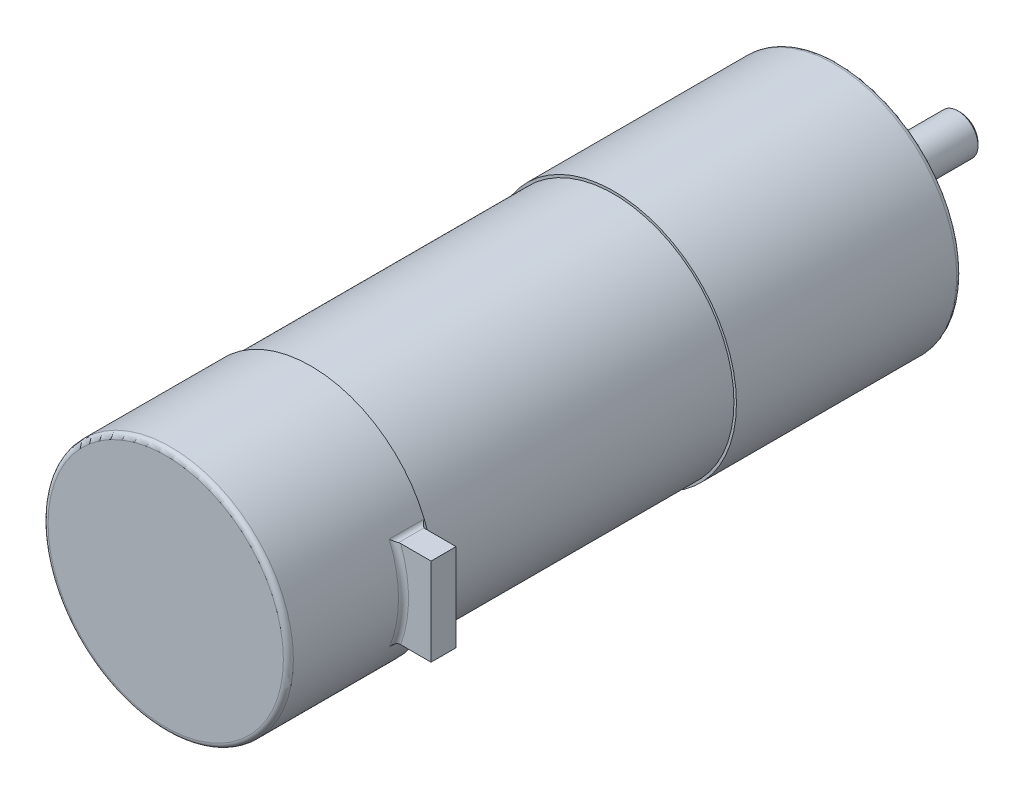
SolidWorks part; units mm, degrees
material "6061-T6 (SS)"
ref_plane "Front Plane" through (0, 0, 0) normal (0, 0, 1) x (1, 0, 0)
ref_plane "Top Plane" through (0, 0, 0) normal (0, 1, 0) x (1, 0, 0)
ref_plane "Right Plane" through (0, 0, 0) normal (1, 0, 0) x (0, 0, -1)
sketch "Sketch1" plane through (0, 0, 0) normal (0, 0, 1) x (1, 0, 0)
  circle A0 centre (0, 0) radius 12.446
  dimension "D1" = 24.892
extrude "Boss-Extrude1" add sketch "Sketch1" along normal blind 22.86
sketch "Sketch2" plane through (0, 0, 22.86) normal (0, 0, 1) x (1, 0, 0)
  circle A0 centre (0, 0) radius 12.192
  dimension "D1" = 24.384
extrude "Boss-Extrude2" add sketch "Sketch2" along normal blind 30.734
sketch "Sketch3" plane through (0, 0, 53.594) normal (0, 0, 1) x (1, 0, 0)
  circle A0 centre (0, 0) radius 12.446
  dimension "D1" = 24.892
extrude "Boss-Extrude3" add sketch "Sketch3" along normal blind 14.732
sketch "Sketch4" plane through (0, 0, 0) normal (0, 0, -1) x (-1, 0, 0)
  circle A0 centre (0, 0) radius 3.5179
  dimension "D1" = 7.0358
extrude "Boss-Extrude4" add sketch "Sketch4" along normal blind 2.794
sketch "Sketch5" plane through (0, 0, 0) normal (0, 0, -1) x (-1, 0, 0)
  circle A0 centre (0, 0) radius 2.032
  dimension "D1" = 4.064
extrude "Boss-Extrude5" add sketch "Sketch5" along normal blind 12.319
chamfer "Chamfer1" distance 0.254 angle 45 1 edges at (-2.032, 0, -12.319)
fillet "Fillet1" radius 0.635 1 edges at (-3.5179, 0, -2.794)
fillet "Fillet2" radius 0.254 1 edges at (-3.5179, 0, 0)
fillet "Fillet3" radius 0.508 2 edges at (12.446, 0, 68.326) (12.446, 0, 0)
sketch "Sketch6" plane through (0, 0, 0) normal (0, 0, -1) x (-1, 0, 0)
  line L0 (0, 0) -> (0, 12.446) construction
  line L1 (-8.89, 0) -> (0, 0) construction
  circle A0 centre (-8.89, 0) radius 1.5
  circle A1 centre (0, 0) radius 12.446 construction
  circle A2 centre (8.89, 0) radius 1.5
  dimension "D1" = 3
  dimension "D2" = 8.89
extrude "Cut-Extrude1" cut sketch "Sketch6" against normal blind 7.62
sketch "Sketch7" plane through (0, 0, 0) normal (1, 0, 0) x (0, -1, 0)
  line L0 (-4.445, -54.102) -> (4.445, -54.102)
  line L1 (4.445, -54.102) -> (4.445, -56.642)
  line L2 (4.445, -56.642) -> (-4.445, -56.642)
  line L3 (-4.445, -56.642) -> (-4.445, -54.102)
  line L4 (0, -68.326) -> (0, 49931.674) construction
  line L5 (-11.938, -68.326) -> (11.938, -68.326) construction
  line L6 (12.446, -53.594) -> (-12.446, -53.594) construction
  point P5 (0, -54.102)
  point P11 (0, -68.326)
  dimension "D1" = 8.89
  dimension "D2" = 2.54
  dimension "D3" = 0.508
extrude "Boss-Extrude6" add sketch "Sketch7" along normal blind 15.24
fillet "Fillet4" radius 0.508 4 edges at (11.6252, -4.445, 55.372) (12.446, 0, 54.102) (11.6252, 4.445, 55.372) (12.446, 0, 56.642)
